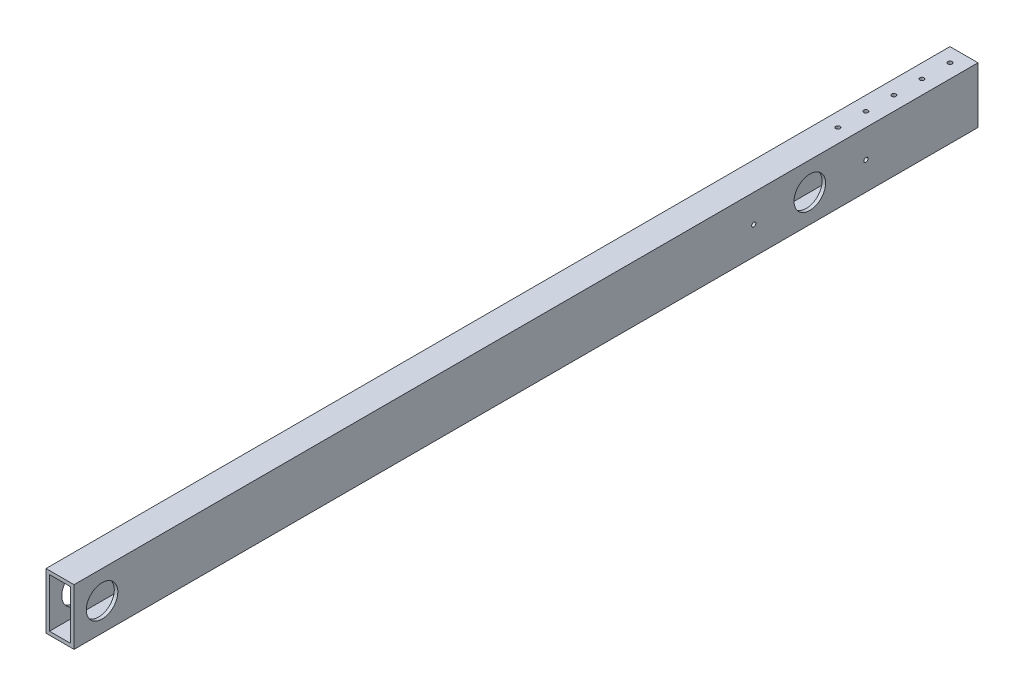
SolidWorks part; units mm, degrees
material "6061-T6 (SS)"
ref_plane "Front Plane" through (0, 0, 0) normal (0, 0, 1) x (1, 0, 0)
ref_plane "Top Plane" through (0, 0, 0) normal (0, 1, 0) x (1, 0, 0)
ref_plane "Right Plane" through (0, 0, 0) normal (1, 0, 0) x (0, 0, -1)
sketch "Sketch1" plane through (0, 0, 0) normal (0, 0, 1) x (1, 0, 0)
  line L0 (-9.525, 22.225) -> (9.525, 22.225)
  line L1 (-12.7, 25.4) -> (12.7, 25.4)
  line L2 (-12.7, 25.4) -> (-12.7, -25.4)
  line L3 (-12.7, -25.4) -> (12.7, -25.4)
  line L4 (12.7, 25.4) -> (12.7, -25.4)
  line L5 (-12.7, 25.4) -> (12.7, -25.4) construction
  line L6 (-12.7, -25.4) -> (12.7, 25.4) construction
  line L7 (9.525, 22.225) -> (9.525, -22.225)
  line L8 (-9.525, -22.225) -> (9.525, -22.225)
  line L9 (-9.525, 22.225) -> (-9.525, -22.225)
  point P0 (0, 0)
  dimension "D1" = 50.8
  dimension "D2" = 25.4
  dimension "D3" = 3.175
extrude "Boss-Extrude1" add sketch "Sketch1" along normal mid plane 819.15
sketch "Sketch7" plane through (0, 25.4, 0) normal (0, 1, 0) x (1, 0, 0)
  line L0 (-12.7, -409.575) -> (-12.7, 409.575) construction
  line L1 (12.7, 409.575) -> (-12.7, 409.575) construction
  circle A0 centre (0, 396.875) radius 1.905
  circle A1 centre (0, 371.475) radius 1.905
  circle A2 centre (0, 346.075) radius 1.905
  circle A3 centre (0, 320.675) radius 1.905
  circle A4 centre (0, 295.275) radius 1.905
  dimension "D1" = 3.81
  dimension "D2" = 12.7
  dimension "D3" = 12.7
  dimension "D4" = 5
extrude "Cut-Extrude1" cut sketch "Sketch7" against normal through all
sketch "Sketch8" plane through (12.7, 0, 0) normal (1, 0, 0) x (0, 0, -1)
  line L0 (409.575, -25.4) -> (409.575, 25.4) construction
  line L1 (-409.575, 25.4) -> (409.575, 25.4) construction
  line L2 (-409.575, -25.4) -> (-409.575, 25.4) construction
  circle A0 centre (206.375, 0) radius 1.905
  circle A1 centre (307.975, 0) radius 1.905
  circle A2 centre (257.175, 0) radius 14.2875
  circle A3 centre (-384.175, 0) radius 14.2875
  dimension "D1" = 3.81
  dimension "D4" = 28.575
  dimension "D6" = 25.4
  dimension "D8" = 50.8
  dimension "D3" = 203.2
  dimension "D5" = 25.4
  dimension "D7" = 25.4
  dimension "D2" = 2
extrude "Cut-Extrude2" cut sketch "Sketch8" against normal through all
